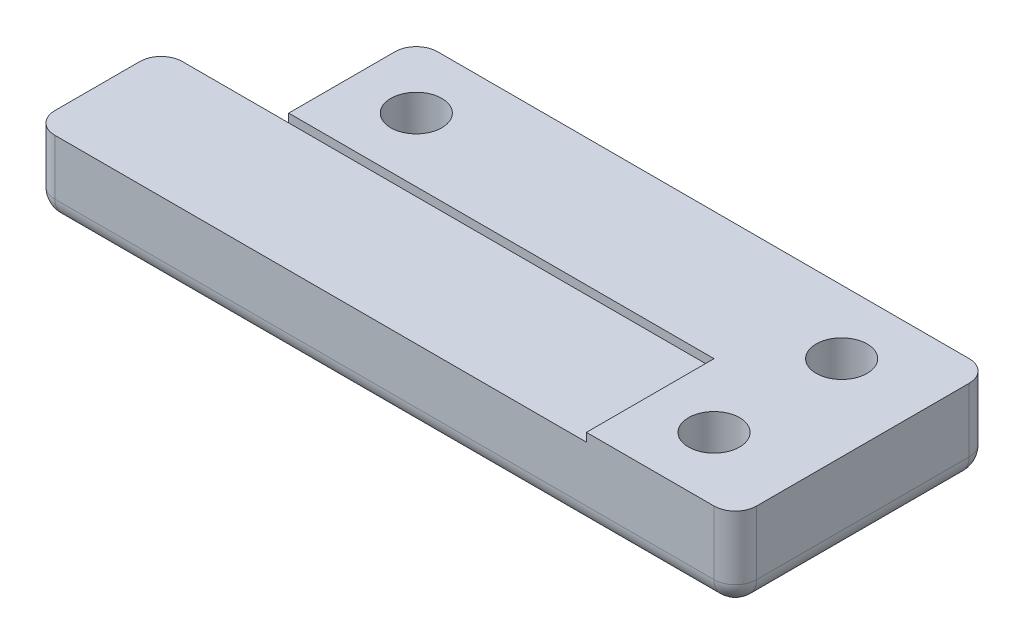
SolidWorks part; units mm, degrees
ref_plane "前基準面" through (0, 0, 0) normal (0, 0, 1) x (1, 0, 0)
ref_plane "上基準面" through (0, 0, 0) normal (0, 1, 0) x (1, 0, 0)
ref_plane "右基準面" through (0, 0, 0) normal (1, 0, 0) x (0, 0, -1)
sketch "草圖1" plane through (0, 0, 0) normal (0, 1, 0) x (1, 0, 0)
  line L1 (-13, -6) -> (20, -6)
  line L2 (-13, -6) -> (-13, 0)
  line L3 (-7, 6) -> (20, 6)
  line L4 (20, -6) -> (20, 6)
  line L5 (-7, 6) -> (-7, 0)
  line L6 (-7, 0) -> (-13, 0)
  line L7 (20, -6) -> (-13, -6) construction
  line L8 (20, -6) -> (20, 6) construction
  line L9 (20, 6) -> (-7, 6) construction
  line L10 (-13, -6) -> (-13, 0) construction
  dimension "D1" = 12
  dimension "D2" = 6
  dimension "D3" = 20
  dimension "D4" = 33
  dimension "D5" = 6
  dimension "D6" = 6
extrude "填料-伸長1" add sketch "草圖1" along normal blind 4
sketch "草圖2" plane through (0, 0, 0) normal (0, 1, 0) x (1, 0, 0)
  line L1 (20, -6) -> (-12, -6) construction
  line L2 (20, -6) -> (20, 6) construction
  line L3 (20, 6) -> (-12, 6) construction
  line L4 (-12, -6) -> (-12, 6) construction
  line L8 (-1.5982, 3) -> (-2.7991, 5.08)
  line L9 (-2.7991, 5.08) -> (-5.2009, 5.08)
  line L10 (-5.2009, 5.08) -> (-6.4018, 3)
  line L11 (-6.4018, 3) -> (-5.2009, 0.92)
  line L12 (-5.2009, 0.92) -> (-2.7991, 0.92)
  line L13 (-2.7991, 0.92) -> (-1.5982, 3)
  circle A0 centre (-4, 3) radius 2.08 construction
  dimension "D1" = 12
  dimension "D2" = 32
extrude "除料-伸長2" cut sketch "草圖2" along normal blind 2 from offset 2
sketch "草圖3" plane through (0, 0, 0) normal (0, 1, 0) x (1, 0, 0)
  line L0 (0, 0) -> (16, 0) construction
  line L1 (20, -6) -> (-12, -6) construction
  line L2 (20, -6) -> (20, 6) construction
  line L3 (20, 6) -> (-12, 6) construction
  line L4 (-12, -6) -> (-12, 6) construction
  line L5 (16, 0) -> (16, -3) construction
  line L7 (13.5982, -3) -> (14.7991, -5.08)
  line L8 (14.7991, -5.08) -> (17.2009, -5.08)
  line L9 (17.2009, -5.08) -> (18.4018, -3)
  line L10 (18.4018, -3) -> (17.2009, -0.92)
  line L11 (17.2009, -0.92) -> (14.7991, -0.92)
  line L12 (14.7991, -0.92) -> (13.5982, -3)
  circle A0 centre (16, -3) radius 2.08 construction
  dimension "D1" = 32
  dimension "D2" = 12
extrude "除料-伸長3" cut sketch "草圖3" along normal blind 2 from offset 2
sketch "草圖4" plane through (0, 0, 0) normal (0, 1, 0) x (1, 0, 0)
  line L0 (0, 0) -> (-4, 0) construction
  line L1 (-4, 0) -> (-4, 3) construction
  line L2 (0, 0) -> (16, 0) construction
  line L3 (16, 0) -> (16, -3) construction
  circle A0 centre (-4, 3) radius 1.2
  circle A1 centre (16, 3) radius 1.2
  circle A2 centre (16, -3) radius 1.2
  dimension "D1" = 4
  dimension "D3" = 16
  dimension "D2" = 3
  dimension "D4" = 3
extrude "除料-伸長4" cut sketch "草圖4" along normal through all
fillet "圓角1" radius 1 11 edges at (-7, 4, -3) (-10, 4, 0) (-13, 4, 3) (3.5, 4, 6) (20, 4, 0) (6.5, 4, -6) (-13, 2, 0) (-13, 2, 6) (20, 2, 6) (20, 2, -6) (-7, 2, -6)
sketch "草圖6" plane through (0, 0, 0) normal (0, 1, 0) x (1, 0, 0)
  line L0 (19, -6) -> (-12, -6) construction
  line L1 (-13, -6) -> (13, -6)
  line L2 (-13, -6) -> (-13, 0)
  line L3 (-13, 0) -> (13, 0)
  line L4 (13, -6) -> (13, 0)
  line L5 (-7, 0) -> (-7, 5) construction
  dimension "D1" = 26
  dimension "D2" = 6
  dimension "D3" = 0
  dimension "D4" = 6
extrude "除料-伸長8" cut sketch "草圖6" along normal blind 0.4
mirror "鏡射3" about plane through (-7, 4, 0) normal (0, 0, 1) of "除料-伸長3"
mirror "鏡射2" about plane through (0, 0, 0) normal (0, 1, 0) of "鏡射3", "除料-伸長8", "圓角1", "除料-伸長4", "除料-伸長3", "除料-伸長2", "填料-伸長1"
sketch "草圖8" plane through (0, 0, 0) normal (0, 1, 0) x (1, 0, 0)
  line L1 (-30.6598, 22.8737) -> (29.8612, 22.8737)
  line L2 (-30.6598, 22.8737) -> (-30.6598, -15.1705)
  line L3 (-30.6598, -15.1705) -> (29.8612, -15.1705)
  line L4 (29.8612, 22.8737) -> (29.8612, -15.1705)
extrude "除料-伸長10" cut sketch "草圖8" along normal blind 26
